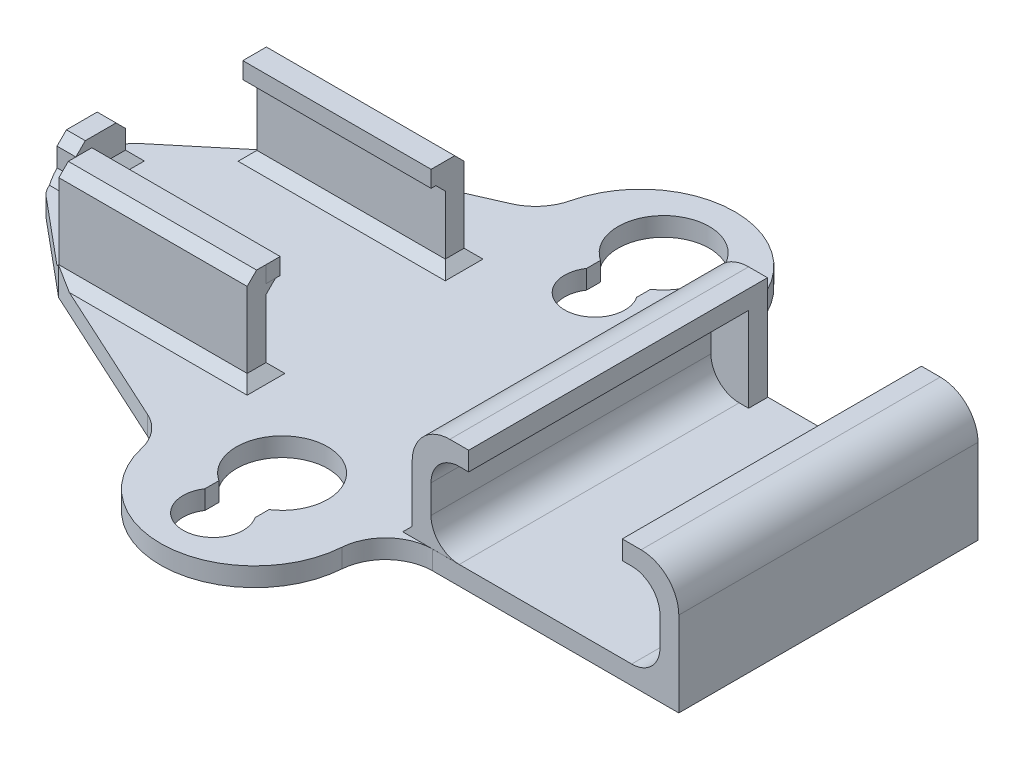
SolidWorks part; units mm, degrees
ref_plane "Front Plane" through (0, 0, 0) normal (0, 0, 1) x (1, 0, 0)
ref_plane "Top Plane" through (0, 0, 0) normal (0, 1, 0) x (1, 0, 0)
ref_plane "Right Plane" through (0, 0, 0) normal (1, 0, 0) x (0, 0, -1)
sketch "Sketch1" plane through (0, 0, 0) normal (0, 1, 0) x (1, 0, 0)
  line L0 (1.6716, 17.1781) -> (1.6716, -5.8219) construction
  line L1 (-11.9265, 14.1796) -> (-8.3284, 17.1781)
  line L2 (21.6629, -19.4069) -> (21.6629, -12.0976)
  line L3 (11.6716, -5.8219) -> (-8.3284, -5.8219) construction
  line L4 (62.7596, 20.6523) -> (62.7596, -11.0972)
  line L5 (-17.3284, 8.273) -> (-17.3284, 3.0832)
  line L6 (-11.9265, 14.1796) -> (-16.2489, 10.5776)
  line L7 (-16.2489, 0.7785) -> (-11.9265, -2.8235)
  line L8 (1.6716, 5.6781) -> (-25.0675, 5.6781) construction
  line L9 (24.3206, -17.6245) -> (24.3206, -16.1442)
  line L10 (19.0053, -17.6245) -> (19.0053, -16.1442)
  line L11 (24.3206, 22.8677) -> (24.3206, 24.3481)
  line L12 (19.0053, 22.8677) -> (19.0053, 24.3481)
  line L13 (21.6629, 21.9934) -> (21.6629, 29.3026)
  line L14 (36.4596, 20.6523) -> (36.4596, -11.0972) construction
  line L17 (-8.3284, 17.1781) -> (9.0724, 24.8143)
  line L18 (11.4596, 17.1781) -> (-8.3284, 17.1781) construction
  line L19 (-11.9265, -2.8235) -> (-8.3284, -5.8219)
  line L20 (-8.3284, -5.8219) -> (9.1456, -13.8508)
  line L21 (60.7596, 20.6523) -> (60.7596, -11.0972) construction
  line L22 (36.4596, 20.6523) -> (62.7596, 20.6523)
  line L23 (36.4596, -11.0972) -> (62.7596, -11.0972)
  line L24 (36.4596, 20.6523) -> (36.66, 20.6523)
  line L25 (36.4596, -11.0972) -> (36.6323, -11.0972)
  arc A0 (19.0053, -17.6245) -> (24.3206, -17.6245) centre (21.6629, -19.4069) ccw
  arc A1 (24.3206, -16.1442) -> (19.0053, -16.1442) centre (21.6629, -12.0976) ccw
  arc A2 (24.3206, 24.3481) -> (19.0053, 24.3481) centre (21.6629, 28.3947) ccw
  arc A3 (19.0053, 22.8677) -> (24.3206, 22.8677) centre (21.6629, 21.0854) ccw
  arc A4 (31.661, 25.7519) -> (11.9297, 28.2456) centre (21.6629, 25.9512) ccw
  arc A5 (11.9292, -17.2666) -> (31.6454, -15.7353) centre (21.6716, -15.0114) ccw
  arc A6 (11.9292, -17.2666) -> (9.1456, -13.8508) centre (7.058, -18.3941) ccw
  arc A7 (9.0724, 24.8143) -> (11.9297, 28.2456) centre (7.0631, 29.3928) ccw
  arc A8 (-16.2489, 0.7785) -> (-17.3284, 3.0832) centre (-14.3284, 3.0832) cw
  arc A9 (-16.2489, 10.5776) -> (-17.3284, 8.273) centre (-14.3284, 8.273) ccw
  arc A10 (31.6454, -15.7353) -> (36.6323, -11.0972) centre (36.6323, -16.0972) cw
  arc A11 (31.661, 25.7519) -> (36.66, 20.6523) centre (36.66, 25.6523) ccw
  point P30 (11.6629, 25.9512)
  point P35 (-17.3284, 1.6781)
  point P38 (-17.3284, 9.6781)
  dimension "D1" = 5
  dimension "D2" = 3
  dimension "D7" = 5
  dimension "D3" = 19
  dimension "D4" = 8
  dimension "D5" = 25
  dimension "D6" = 24.3
  dimension "D8" = 2
extrude "Boss-Extrude3" add sketch "Sketch1" along normal blind 2 contours L6 A9 L5 A8 L7 A5 A4 A1 L9 A0 L10 A3 L12 A2 L11 region at (24.7899, 0, -5.2127)
sketch "Sketch2" plane through (0, 2, 0) normal (0, 1, 0) x (1, 0, 0)
  line L1 (-17.3284, 8.273) -> (-15.3284, 8.273)
  line L2 (-17.3284, 8.273) -> (-17.3284, 3.0832)
  line L3 (-17.3284, 3.0832) -> (-15.3284, 3.0832)
  line L4 (-15.3284, 8.273) -> (-15.3284, 3.0832)
  line L5 (11.6543, 17.2264) -> (-8.3284, 17.2264)
  line L6 (11.6543, 17.2264) -> (11.6543, 15.2264)
  line L7 (11.6543, 15.2264) -> (-8.3284, 15.2264)
  line L8 (-8.3284, 17.2264) -> (-8.3284, 15.2264)
  line L9 (11.6629, 25.9512) -> (11.6716, -15.0114) construction
  line L10 (11.6519, -5.7923) -> (-8.3284, -5.7923)
  line L11 (11.6519, -5.7923) -> (11.6519, -3.7923)
  line L12 (11.6519, -3.7923) -> (-8.3284, -3.7923)
  line L13 (-8.3284, -5.7923) -> (-8.3284, -3.7923)
  dimension "D1" = 2
  dimension "D2" = 2
  dimension "D3" = 2
extrude "Boss-Extrude4" add sketch "Sketch2" along normal blind 10 contours L5 L8 L7 L6 | L10 L13 L12 L11
sketch "Sketch4" plane through (0, 0, -15.2264) normal (0, 0, 1) x (1, 0, 0)
  line L0 (11.6543, 12) -> (11.6543, 2) construction
  line L1 (-8.3284, 12) -> (11.6543, 12)
  line L2 (-8.3284, 12) -> (-8.3284, 10.25)
  line L3 (-8.3284, 10.25) -> (11.6543, 10.25)
  line L4 (11.6543, 12) -> (11.6543, 10.25)
  dimension "D1" = 1.75
extrude "Boss-Extrude6" add sketch "Sketch4" along normal blind 1.5
sketch "Sketch5" plane through (0, 0, 3.7923) normal (0, 0, -1) x (-1, 0, 0)
  line L1 (8.3284, 12) -> (-11.6543, 12)
  line L2 (8.3284, 12) -> (8.3284, 10.25)
  line L3 (8.3284, 10.25) -> (-11.6543, 10.25)
  line L4 (-11.6543, 12) -> (-11.6543, 10.25)
  dimension "D1" = 1.75
extrude "Boss-Extrude7" add sketch "Sketch5" along normal blind 1.5
sketch "Sketch6" plane through (0, 2, 0) normal (0, 1, 0) x (1, 0, 0)
  line L1 (62.7596, -11.0972) -> (36.6323, -11.0972) construction
  line L4 (36.4596, 20.6109) -> (34.4596, 20.6109)
  line L5 (36.4596, 20.6109) -> (36.4596, -11.0927)
  line L6 (36.4596, -11.0927) -> (34.4596, -11.0927)
  line L7 (34.4596, 20.6109) -> (34.4596, -11.0927)
  line L8 (62.7596, 20.6523) -> (60.7596, 20.6523)
  line L9 (62.7596, 20.6523) -> (62.7596, -11.0972)
  line L10 (62.7596, -11.0972) -> (60.7596, -11.0972)
  line L11 (60.7596, 20.6523) -> (60.7596, -11.0972)
  dimension "D1" = 2
  dimension "D2" = 24.3
  dimension "D3" = 2
extrude "Boss-Extrude8" add sketch "Sketch6" along normal blind 11
sketch "Sketch7" plane through (60.7596, 0, 0) normal (-1, 0, 0) x (0, 0, 1)
  line L0 (-20.6523, 13) -> (-20.6523, 2) construction
  line L1 (11.0972, 13) -> (-20.6523, 13)
  line L2 (11.0972, 13) -> (11.0972, 11)
  line L3 (11.0972, 11) -> (-20.6523, 11)
  line L4 (-20.6523, 13) -> (-20.6523, 11)
  dimension "D1" = 2
extrude "Boss-Extrude9" add sketch "Sketch7" along normal blind 4
sketch "Sketch8" plane through (36.4596, 0, 0) normal (1, 0, 0) x (0, 0, -1)
  line L1 (-11.0927, 13) -> (20.6109, 13)
  line L2 (-11.0927, 13) -> (-11.0927, 11)
  line L3 (-11.0927, 11) -> (20.6109, 11)
  line L4 (20.6109, 13) -> (20.6109, 11)
  line L5 (-11.0927, 13) -> (20.6109, 13) construction
  line L6 (20.6109, 13) -> (20.6109, 2) construction
  dimension "D1" = 2
extrude "Boss-Extrude10" add sketch "Sketch8" along normal blind 4
sketch "Sketch9" plane through (36.4596, 0, 0) normal (1, 0, 0) x (0, 0, -1)
  line L0 (-11.0927, 2) -> (20.6109, 2) construction
  line L1 (20.6109, 11) -> (18.6109, 11)
  line L2 (20.6109, 11) -> (20.6109, 2)
  line L3 (20.6109, 2) -> (18.6109, 2)
  line L4 (18.6109, 11) -> (18.6109, 2)
  dimension "D1" = 2
extrude "Boss-Extrude11" add sketch "Sketch9" along normal blind 4
sketch "Sketch11" plane through (60.7596, 0, 0) normal (-1, 0, 0) x (0, 0, 1)
  line L0 (-20.6523, 11) -> (-20.6523, 2) construction
  line L1 (-20.6523, 11) -> (-18.6523, 11)
  line L2 (-20.6523, 11) -> (-20.6523, 2)
  line L3 (-20.6523, 2) -> (-18.6523, 2)
  line L4 (-18.6523, 11) -> (-18.6523, 2)
  line L5 (-20.6523, 2) -> (11.0972, 2) construction
  dimension "D1" = 2
extrude "Boss-Extrude12" add sketch "Sketch11" along normal blind 4
fillet "Fillet3" radius 3 4 edges at (60.7596, 2, -3.7776) (60.7596, 11, -3.7776) (36.4596, 2, -3.7591) (36.4596, 11, -3.7591)
fillet "Fillet4" radius 4 1 edges at (62.7596, 13, -4.7776)
fillet "Fillet5" radius 4 1 edges at (34.4596, 13, -4.7591)
chamfer "Chamfer3" distance 1 angle 45 3 edges at (34.4596, 2, -4.7591) (1.6618, 2, 5.7923) (1.718, 2, -17.2264)
sketch "Sketch13" plane through (0, 2, 0) normal (0, 1, 0) x (1, 0, 0)
  line L1 (-17.3284, 8.273) -> (-15.3284, 8.273)
  line L2 (-17.3284, 8.273) -> (-17.3284, 3.0096)
  line L3 (-17.3284, 3.0096) -> (-15.3284, 3.0096)
  line L4 (-15.3284, 8.273) -> (-15.3284, 3.0096)
  dimension "D1" = 2
extrude "Boss-Extrude13" add sketch "Sketch13" along normal blind 4
chamfer "Chamfer4" distance 1 angle 45 13 edges at (1.6618, 12, 5.7923) (1.663, 12, -17.2264) (1.663, 10.25, -15.2264) (1.6618, 10.25, 3.7923) (-16.3284, 2, -8.273) (-16.3279, 2, -3.0096) (-15.3284, 2, -5.6413) (11.6519, 2, 5.2923) (-8.3284, 2, 4.8071) (1.6618, 2, 3.7923) (11.6543, 2, -16.7264) (-8.3284, 2, -16.2023) (1.663, 2, -15.2264)
chamfer "Chamfer5" distance 1 angle 45 2 edges at (-16.3284, 6, -8.273) (-16.3284, 6, -3.0096)
